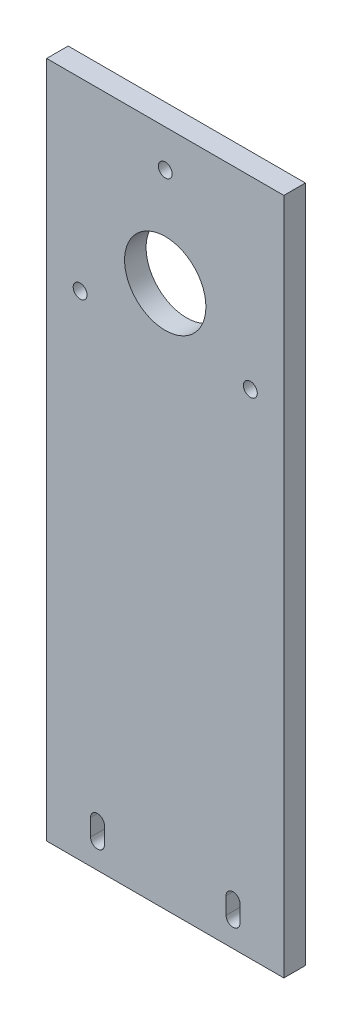
SolidWorks part; units mm, degrees
ref_plane "Front Plane" through (0, 0, 0) normal (0, 0, 1) x (1, 0, 0)
ref_plane "Top Plane" through (0, 0, 0) normal (0, 1, 0) x (1, 0, 0)
ref_plane "Right Plane" through (0, 0, 0) normal (1, 0, 0) x (0, 0, -1)
sketch "Sketch1" plane through (0, 0, 0) normal (0, 0, 1) x (1, 0, 0)
  line L0 (0, 100) -> (0, -100) construction
  line L1 (-35, -100) -> (35, -100)
  line L2 (-35, -100) -> (-35, 100)
  line L3 (-35, 100) -> (35, 100)
  line L4 (35, -100) -> (35, 100)
  line L5 (-35, -100) -> (35, 100) construction
  line L6 (-35, 100) -> (35, -100) construction
  line L7 (-20, -92.5) -> (-20, -87.5) construction
  line L8 (-22.05, -92.5) -> (-22.05, -87.5)
  line L9 (-17.95, -92.5) -> (-17.95, -87.5)
  line L10 (20, -92.5) -> (20, -87.5) construction
  line L11 (22.05, -92.5) -> (22.05, -87.5)
  line L12 (17.95, -92.5) -> (17.95, -87.5)
  circle A0 centre (0, 60) radius 33.35 construction
  circle A1 centre (0, 60) radius 29 construction
  circle A2 centre (0, 89) radius 2.05
  circle A3 centre (25.1147, 45.5) radius 2.05
  circle A4 centre (-25.1147, 45.5) radius 2.05
  circle A5 centre (-20, -90) radius 2.05 construction
  arc A6 (-22.05, -92.5) -> (-17.95, -92.5) centre (-20, -92.5) ccw
  arc A7 (-17.95, -87.5) -> (-22.05, -87.5) centre (-20, -87.5) ccw
  arc A8 (22.05, -92.5) -> (17.95, -92.5) centre (20, -92.5) cw
  arc A9 (17.95, -87.5) -> (22.05, -87.5) centre (20, -87.5) cw
  circle A10 centre (0, 60) radius 12
  point P0 (0, 0)
  point P19 (0, 60)
  point P22 (-20, -90)
  point P34 (20, -90)
  dimension "D3" = 66.7
  dimension "D4" = 40
  dimension "D5" = 58
  dimension "D6" = 4.1
  dimension "D8" = 4.1
  dimension "D9" = 15
  dimension "D10" = 5
  dimension "D12" = 24
  dimension "D1" = 70
  dimension "D2" = 200
  dimension "D11" = 10
  dimension "D7" = 3
extrude "Boss-Extrude1" add sketch "Sketch1" along normal blind 6.35
